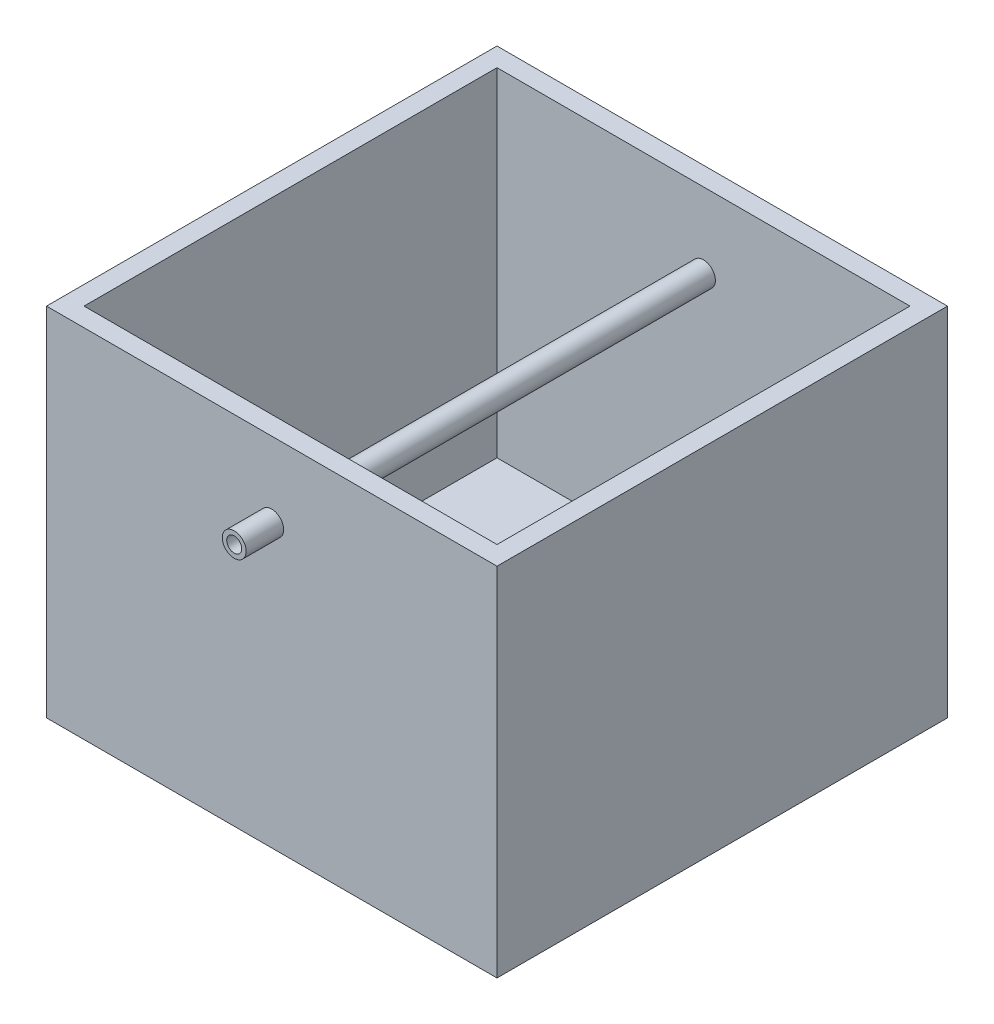
SolidWorks part; units mm, degrees
ref_plane "Front Plane" through (0, 0, 0) normal (0, 0, 1) x (1, 0, 0)
ref_plane "Top Plane" through (0, 0, 0) normal (0, 1, 0) x (1, 0, 0)
ref_plane "Right Plane" through (0, 0, 0) normal (1, 0, 0) x (0, 0, -1)
sketch "Sketch1" plane through (0, 0, 0) normal (0, 1, 0) x (1, 0, 0)
  line L1 (-60, -60) -> (60, -60)
  line L2 (-60, -60) -> (-60, 60)
  line L3 (-60, 60) -> (60, 60)
  line L4 (60, -60) -> (60, 60)
  line L5 (-60, -60) -> (60, 60) construction
  line L6 (-60, 60) -> (60, -60) construction
  point P0 (0, 0)
  dimension "D1" = 120
  dimension "D2" = 120
extrude "Boss-Extrude1" add sketch "Sketch1" along normal blind 150
shell "Shell1" thickness 5 removed face at (0, 150, 0)
sketch "Sketch2" plane through (0, 0, 60) normal (0, 0, 1) x (1, 0, 0)
  circle A0 centre (0, 75) radius 3.175
  circle A1 centre (0, 75) radius 2
  dimension "D1" = 6.35
  dimension "D2" = 4
extrude "Boss-Extrude2" add sketch "Sketch2" along normal blind 10 and the other way blind 116
sketch "Sketch3" plane through (0, 5, 0) normal (0, 1, 0) x (1, 0, 0)
  circle A0 centre (0, 0) radius 1
  circle A1 centre (0, 7.5) radius 1
  circle A2 centre (0, -7.5) radius 1
  circle A3 centre (0, -15) radius 1
  circle A4 centre (0, 15) radius 1
  circle A5 centre (0, -22.5) radius 1
  circle A6 centre (0, 22.5) radius 1
  circle A7 centre (0, -30) radius 1
  circle A8 centre (0, 30) radius 1
  circle A9 centre (0, -37.5) radius 1
  circle A10 centre (0, 37.5) radius 1
  circle A11 centre (0, -45) radius 1
  circle A12 centre (0, 45) radius 1
  point P27 (0, 0)
  dimension "D1" = 2
  dimension "D2" = 2
  dimension "D3" = 2
  dimension "D4" = 2
  dimension "D5" = 2
  dimension "D6" = 2
  dimension "D7" = 2
  dimension "D8" = 2
  dimension "D9" = 2
  dimension "D10" = 2
  dimension "D11" = 2
  dimension "D23" = 2
  dimension "D24" = 2
  dimension "D12" = 37.5
  dimension "D13" = 30
  dimension "D14" = 22.5
  dimension "D15" = 15
  dimension "D16" = 7.5
  dimension "D17" = 7.5
  dimension "D18" = 15
  dimension "D19" = 22.5
  dimension "D20" = 30
  dimension "D21" = 37.5
  dimension "D22" = 45
  dimension "D25" = 45
extrude "Cut-Extrude1" cut sketch "Sketch3" along normal blind 70
sketch "Sketch4" plane through (0, 0, 60) normal (0, 0, 1) x (1, 0, 0)
  line L0 (60, 150) -> (60, 0) construction
  line L1 (-60, 162.2431) -> (60, 162.2431)
  line L2 (-60, 162.2431) -> (-60, 95)
  line L3 (-60, 95) -> (60, 95)
  line L4 (60, 162.2431) -> (60, 95)
  line L5 (-60, 162.2431) -> (60, 95) construction
  line L6 (-60, 95) -> (60, 162.2431) construction
  circle A0 centre (0, 75) radius 2 construction
  point P0 (0, 128.6215)
  dimension "D1" = 20
extrude "Cut-Extrude2" cut sketch "Sketch4" against normal blind 120
sketch "Sketch5" plane through (-60, 0, 0) normal (-1, 0, 0) x (0, 0, 1)
  circle A0 centre (0, 27.5) radius 2
  circle A1 centre (0, 27.5) radius 3.175
  dimension "D1" = 4
  dimension "D2" = 6.35
extrude "Boss-Extrude3" add sketch "Sketch5" along normal blind 10
sketch "Sketch6" plane through (-60, 0, 0) normal (-1, 0, 0) x (0, 0, 1)
  circle A0 centre (0, 27.5) radius 2
extrude "Cut-Extrude3" cut sketch "Sketch6" against normal blind 10
